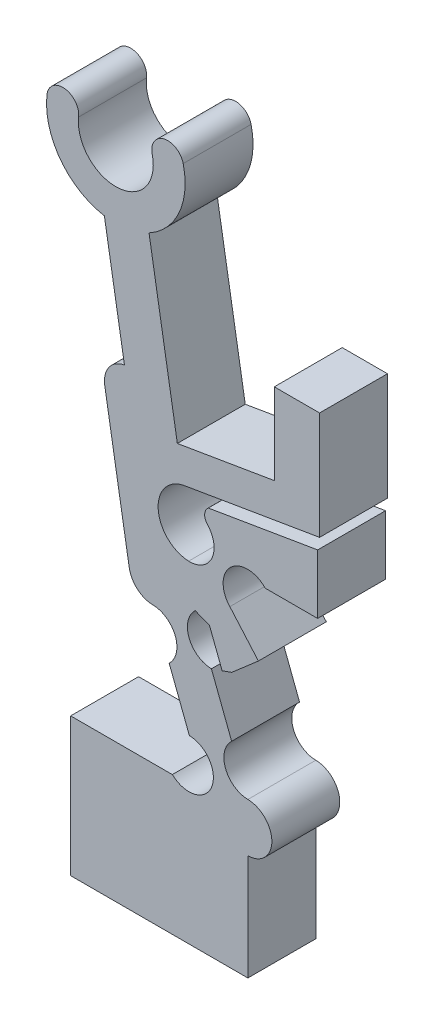
SolidWorks part; units mm, degrees
ref_plane "Front Plane" through (0, 0, 0) normal (0, 0, 1) x (1, 0, 0)
ref_plane "Top Plane" through (0, 0, 0) normal (0, 1, 0) x (1, 0, 0)
ref_plane "Right Plane" through (0, 0, 0) normal (1, 0, 0) x (0, 0, -1)
sketch "Sketch-SkeletonConfigUp" plane through (0, 0, 0) normal (0, 0, 1) x (1, 0, 0)
  line L0 (0, 0) -> (0, -50000) construction
  line L1 (0, 0) -> (4.5811, 6.2164) construction
  line L2 (9.8143, 13.3177) -> (4.5811, 13.945) construction
  line L3 (4.5811, 13.945) -> (2.9713, 10.4094) construction
  line L4 (2.9713, 10.4094) -> (4.5811, 6.2164) construction
  line L5 (4.5811, 13.945) -> (6.2429, 19.1409) construction
  line L6 (2.9713, 10.4094) -> (0.0405, 27.8193) construction
  line L7 (4.5811, 6.2164) -> (9.8143, 13.3177) construction
  line L8 (-587.3593, -797.0242) -> (9.8143, 13.3177) construction
  dimension "D2" = 7.7221
  dimension "D3" = 8.8212
  dimension "D4" = 5.2707
  dimension "D5" = 119.553
  dimension "D6" = 3.8848
  dimension "D7" = 5.4552
  dimension "D8" = 17.6549
  dimension "D9" = 4.4914
  dimension "D10" = 6.745
  dimension "D11" = 145.964
  dimension "D12" = 143.612
sketch "Sketch-SkeletonConfigDown" plane through (0, 0, 0) normal (0, 0, 1) x (1, 0, 0)
  line L0 (0, 0) -> (0, -50000) construction
  line L1 (0, 0) -> (4.5811, 6.2164) construction
  line L2 (9.8143, 13.3177) -> (4.5811, 13.945) construction
  line L3 (4.5811, 13.945) -> (6.1909, 10.4094) construction
  line L4 (6.1909, 10.4094) -> (4.5811, 6.2164) construction
  line L5 (4.5811, 13.945) -> (1.753, 18.6098) construction
  line L6 (6.1909, 10.4094) -> (-8.8652, 19.6294) construction
  line L7 (4.5811, 6.2164) -> (9.8143, 13.3177) construction
  line L8 (-589.9357, -800.5203) -> (9.8143, 13.3177) construction
  dimension "D2" = 7.7221
  dimension "D3" = 8.8212
  dimension "D4" = 5.2707
  dimension "D5" = 119.553
  dimension "D6" = 3.8848
  dimension "D7" = 5.4552
  dimension "D8" = 17.6549
  dimension "D9" = 4.4914
  dimension "D10" = 6.745
  dimension "D11" = 145.964
  dimension "D1" = 143.612
sketch "Sketch-SwitchBossUp" plane through (0, 0, 0) normal (0, 0, 1) x (1, 0, 0)
  line L0 (2.4756, 11.7339) -> (3.2566, 13.4492) construction
  line L1 (4.2958, 10.9051) -> (5.0768, 12.6205) construction
  line L2 (7.0405, 18.4234) -> (7.0405, 22.0106)
  line L3 (7.0405, 22.0106) -> (9.0405, 22.0106)
  line L4 (9.0405, 22.0106) -> (9.0405, 17.2503)
  line L5 (4.5811, 13.945) -> (2.9713, 10.4094) construction
  line L7 (1.507, 25.1315) -> (2.7576, 17.7024)
  line L8 (-0.4652, 24.7995) -> (0.4213, 19.5329)
  line L9 (2.9713, 10.4094) -> (0.0405, 27.8193) construction
  line L10 (4.6863, 11.7628) -> (2.8661, 12.5916) construction
  line L11 (-0.0396, 22.2712) -> (1.9326, 22.6032) construction
  line L12 (7.0405, 17.8756) -> (9.0405, 17.8756) construction
  line L13 (2.3961, 9.1174) -> (3.2891, 6.7916)
  line L14 (4.2633, 9.8343) -> (5.1563, 7.5084)
  line L15 (4.7098, 8.6713) -> (2.8426, 7.9545) construction
  line L16 (2.9713, 10.4094) -> (4.5811, 6.2164) construction
  line L17 (3.2566, 13.4492) -> (4.0854, 15.2694) construction
  line L18 (5.0768, 12.6205) -> (5.9056, 14.4407) construction
  line L19 (4.2853, 14.0796) -> (4.8769, 13.8103) construction
  line L20 (4.0854, 15.2694) -> (5.9056, 14.4407) construction
  line L21 (3.2566, 13.4492) -> (5.0768, 12.6205) construction
  line L22 (4.1667, 13.0349) -> (4.9955, 14.8551) construction
  line L23 (2.4756, 11.7339) -> (4.2958, 10.9051) construction
  line L24 (2.3961, 9.1174) -> (1.6793, 10.9845) construction
  line L25 (4.2633, 9.8343) -> (3.5464, 11.7014) construction
  line L26 (4.2633, 9.8343) -> (2.3961, 9.1174) construction
  line L27 (1.6793, 10.9845) -> (3.5464, 11.7014) construction
  line L28 (3.2891, 6.7916) -> (5.1563, 7.5084) construction
  line L29 (3.2891, 6.7916) -> (4.006, 4.9244) construction
  line L30 (5.1563, 7.5084) -> (5.8731, 5.6413) construction
  line L31 (4.006, 4.9244) -> (5.8731, 5.6413) construction
  line L32 (4.8845, 6.3329) -> (4.2777, 6.0999) construction
  line L36 (0.0405, 27.8193) -> (9.0405, 27.8193) construction
  line L40 (3.2747, 10.5259) -> (2.6679, 10.2929) construction
  line L43 (2.5363, 4.9244) -> (-1.9548, 4.9244)
  line L44 (-1.9548, 4.9244) -> (-1.9548, -1.1895)
  line L45 (-1.9548, -1.1895) -> (5.8731, -1.1895)
  line L46 (5.8731, -1.1895) -> (5.8731, 3.4851)
  line L48 (2.4756, 11.7339) -> (1.6793, 10.9845) construction
  line L51 (7.0405, 18.4234) -> (2.7576, 17.7024)
  line L53 (9.0405, 17.2503) -> (3.0048, 16.2342)
  line L57 (4.1248, 15.9157) -> (8.9557, 16.729)
  line L61 (8.9557, 14.1065) -> (8.9557, 16.729)
  line L63 (4.7371, 9.9951) -> (5.1595, 10.1452)
  line L65 (5.1595, 10.1452) -> (6.338, 11.1696)
  line L66 (6.149, 11.065) -> (6.149, 50011.065) construction
  line L67 (4.7371, 9.9951) -> (4.1779, 11.4515)
  line L68 (3.5464, 11.7014) -> (4.1779, 11.4515)
  line L69 (5.0768, 12.6205) -> (6.338, 11.1696)
  line L71 (6.6395, 14.1065) -> (8.9557, 14.1065)
  line L72 (5.9056, 14.4407) -> (6.6395, 14.1065) construction
  line L74 (0.6325, 11.8929) -> (-0.448, 18.3116)
  line L75 (0.2173, 14.3595) -> (1.9257, 14.6345) construction
  arc A0 (1.507, 25.1315) -> (3.0168, 28.5383) centre (0.0405, 27.8193) ccw
  arc A1 (-0.4652, 24.7995) -> (-3.0011, 28.1713) centre (0.0405, 27.8193) cw
  arc A2 (-3.0011, 28.1713) -> (-1.6023, 28.0095) centre (-2.3017, 28.0904) cw
  arc A3 (3.0168, 28.5383) -> (1.648, 28.2077) centre (2.3324, 28.373) ccw
  arc A4 (-1.6023, 28.0095) -> (1.648, 28.2077) centre (0.0405, 27.8193) ccw
  arc A5 (3.2566, 13.4492) -> (4.0854, 15.2694) centre (3.304, 14.5264) ccw
  arc A6 (5.0768, 12.6205) -> (5.9056, 14.4407) centre (5.8582, 13.3635) cw
  arc A7 (2.3961, 9.1174) -> (1.6793, 10.9845) centre (1.6613, 9.9064) ccw
  arc A8 (3.5464, 11.7014) -> (4.2633, 9.8343) centre (4.2813, 10.9124) ccw
  arc A9 (3.2891, 6.7916) -> (4.006, 4.9244) centre (3.2711, 5.7135) cw
  arc A10 (5.1563, 7.5084) -> (5.8731, 5.6413) centre (5.8911, 6.7194) ccw
  arc A16 (5.9056, 14.4407) -> (6.6395, 14.1065) centre (5.8582, 13.3635) cw
  arc A18 (1.6793, 10.9845) -> (0.6325, 11.8929) centre (1.6973, 12.0626) cw
  arc A19 (-0.448, 18.3116) -> (0.4213, 19.5329) centre (0.5973, 18.4876) cw
  arc A20 (3.2566, 13.4492) -> (3.0048, 16.2342) centre (3.3186, 14.8587) cw
  arc A21 (4.006, 4.9244) -> (2.5363, 4.9244) centre (3.2711, 5.7135) cw
  arc A22 (5.8731, 5.6413) -> (5.8731, 3.4851) centre (5.8551, 4.5632) cw
  arc A23 (4.0854, 15.2694) -> (4.1248, 15.9157) centre (4.4059, 15.5742) cw
  point P29 (3.7762, 12.1772)
  point P44 (3.7762, 8.3129)
  point P53 (4.5811, 13.945)
  point P63 (2.9713, 10.4094)
  dimension "D1" = 2
  dimension "D2" = 2
  dimension "D3" = 2
  dimension "D4" = 2
  dimension "D5" = 2
  dimension "D6" = 0.65
  dimension "D7" = 0.5
  dimension "D8" = 49
  dimension "D9" = 0.5
  dimension "D10" = 9
extrude "Boss-Extrude1" add sketch "Sketch-SwitchBossUp" along normal blind 3
equation "\"axle-diameter\"=2"
equation "\"switch-thickness\"=12"
equation "\"base-width\"=4.0"
equation "\"axle-bushing-radius\"=3"
equation "\"clearance\"= 0.25"
equation "\"arm-width\"=1.5"
equation "\"min-diameter\"=70"
equation "\"alpha\"=143.6120"
equation "\"gamma\"=119.5526"
equation "\"delta\"=145.9637"
equation "\"epsilon\"=6.7452"
equation "\"l_AB\"=8.8212"
equation "\"l_AC\"=4.4914"
equation "\"l_BD\"=5.2707"
equation "\"l_CD\"=3.8848"
equation "\"l_CE\"=17.6549"
equation "\"l_DF\"=5.4552"
equation "\"l_OA\"=7.7221"
equation "\"D2@Sketch-SkeletonConfigUp\" = \"l_OA\""
equation "\"D3@Sketch-SkeletonConfigUp\" = \"l_AB\""
equation "\"D4@Sketch-SkeletonConfigUp\" = \"l_BD\""
equation "\"D5@Sketch-SkeletonConfigUp\" = \"gamma\""
equation "\"D6@Sketch-SkeletonConfigUp\" = \"l_CD\""
equation "\"D7@Sketch-SkeletonConfigUp\" = \"l_DF\""
equation "\"D8@Sketch-SkeletonConfigUp\" = \"l_CE\""
equation "\"D9@Sketch-SkeletonConfigUp\" = \"l_AC\""
equation "\"D_groove\"=3.175"
equation "\"D7@Sketch-SkeletonConfigDown\" = \"l_DF\""
equation "\"D6@Sketch-SkeletonConfigDown\" = \"l_CD\""
equation "\"D2@Sketch-SkeletonConfigDown\" = \"l_OA\""
equation "\"D3@Sketch-SkeletonConfigDown\" = \"l_AB\""
equation "\"D9@Sketch-SkeletonConfigDown\" = \"l_AC\""
equation "\"D8@Sketch-SkeletonConfigDown\" = \"l_CE\""
equation "\"D5@Sketch-SkeletonConfigDown\" = \"gamma\""
equation "\"D4@Sketch-SkeletonConfigDown\" = \"l_BD\""
equation "\"D1@Sketch-SkeletonConfigDown\" = \"alpha\""
equation "\"hinge_length\"=1.5"
equation "\"hinge_depth\"=0.25"
equation "\"D10@Sketch-SkeletonConfigUp\"=\"epsilon\""
equation "\"D11@Sketch-SkeletonConfigUp\"=\"delta\""
equation "\"D12@Sketch-SkeletonConfigUp\"=\"alpha\""
equation "\"D11@Sketch-SkeletonConfigDown\"=\"delta\""
equation "\"D10@Sketch-SkeletonConfigDown\"=\"epsilon\""
equation "\"EE_dx\"=8.9056"
equation "\"EE_dy\"=8.1898"
equation "\"r_groove\"=\"D_groove\"/2"
equation "\"t_wall\"=25.4/16"
equation "\"width_lower\"=\"D_groove\"+\"t_wall\""
equation "\"cable_to_bottom\"=30.6257"
equation "\"switch_EE-up_base_dy\"=24"
equation "\"switch_EE-down_base_dy\"=16"
equation "\"D_axle\"=25.4/8"
equation "\"D_up_to_down\"=19"
equation "\"D_down_to_up\"=25"
equation "\"t_cam_base\"=7.5"
